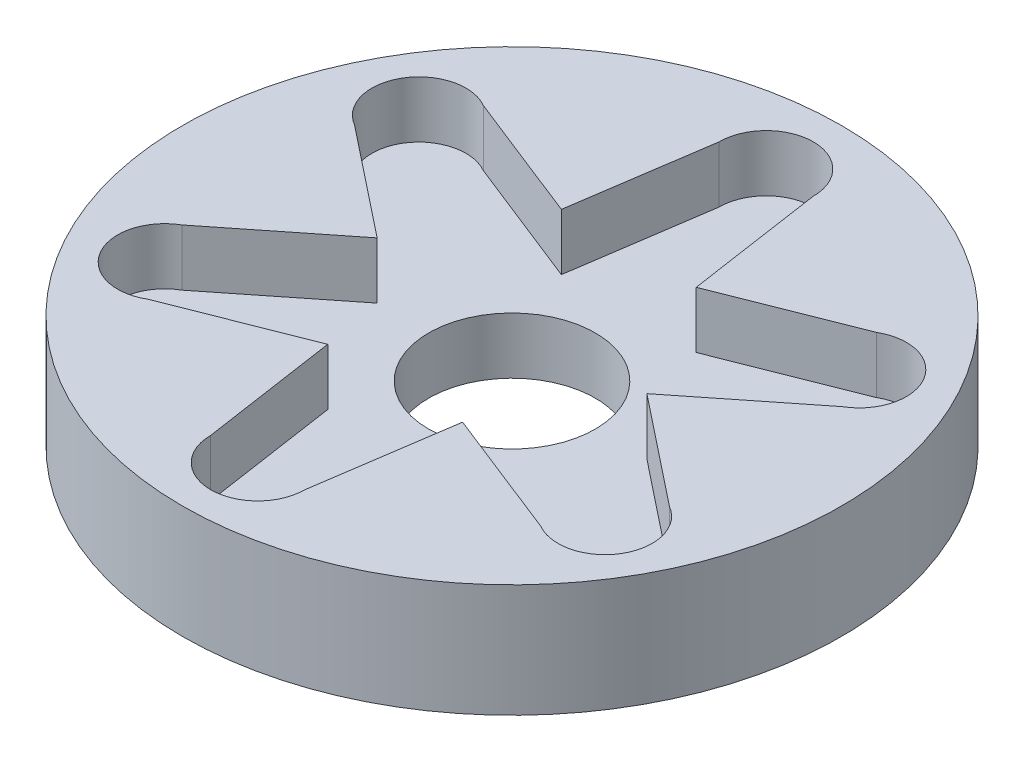
SolidWorks part; units mm, degrees
ref_plane "Front Plane" through (0, 0, 0) normal (0, 0, 1) x (1, 0, 0)
ref_plane "Top Plane" through (0, 0, 0) normal (0, 1, 0) x (1, 0, 0)
ref_plane "Right Plane" through (0, 0, 0) normal (1, 0, 0) x (0, 0, -1)
sketch "Sketch1" plane through (0, 0, 0) normal (0, 1, 0) x (1, 0, 0)
  line L0 (0, 0) -> (0, 16)
  line L2 (0, 13.5) -> (-2.5, 13.5)
  line L3 (0, 13.5) -> (2.5, 13.5)
  line L4 (-2.5, 13.5) -> (-4.5, 0)
  line L5 (2.5, 13.5) -> (4.5, 0)
  line L6 (0, 0) -> (13.8564, 8)
  line L8 (11.6913, 6.75) -> (10.4413, 8.9151)
  line L9 (11.6913, 6.75) -> (12.9413, 4.5849)
  line L10 (10.4413, 8.9151) -> (-2.25, 3.8971)
  line L11 (12.9413, 4.5849) -> (2.25, -3.8971)
  line L12 (0, 0) -> (13.8564, -8)
  line L14 (11.6913, -6.75) -> (12.9413, -4.5849)
  line L15 (11.6913, -6.75) -> (10.4413, -8.9151)
  line L16 (12.9413, -4.5849) -> (2.25, 3.8971)
  line L17 (10.4413, -8.9151) -> (-2.25, -3.8971)
  line L18 (0, 0) -> (0, -16)
  line L20 (0, -13.5) -> (2.5, -13.5)
  line L21 (0, -13.5) -> (-2.5, -13.5)
  line L22 (2.5, -13.5) -> (4.5, 0)
  line L23 (-2.5, -13.5) -> (-4.5, 0)
  line L24 (0, 0) -> (-13.8564, -8)
  line L26 (-11.6913, -6.75) -> (-10.4413, -8.9151)
  line L27 (-11.6913, -6.75) -> (-12.9413, -4.5849)
  line L28 (-10.4413, -8.9151) -> (2.25, -3.8971)
  line L29 (-12.9413, -4.5849) -> (-2.25, 3.8971)
  line L30 (0, 0) -> (-13.8564, 8)
  line L32 (-11.6913, 6.75) -> (-12.9413, 4.5849)
  line L33 (-11.6913, 6.75) -> (-10.4413, 8.9151)
  line L34 (-12.9413, 4.5849) -> (-2.25, -3.8971)
  line L35 (-10.4413, 8.9151) -> (2.25, 3.8971)
  circle A1 centre (0, 13.5) radius 2.5
  circle A3 centre (11.6913, 6.75) radius 2.5
  circle A5 centre (11.6913, -6.75) radius 2.5
  circle A7 centre (0, -13.5) radius 2.5
  circle A9 centre (-11.6913, -6.75) radius 2.5
  circle A10 centre (0, 0) radius 4.425
  circle A11 centre (-11.6913, 6.75) radius 2.5
  circle A12 centre (0, 0) radius 17.5
  point P53 (0, 0)
  dimension "D1" = 8.85
  dimension "D7" = 35
  dimension "D2" = 16
  dimension "D3" = 2.5
  dimension "D4" = 2.5
  dimension "D5" = 2.5
  dimension "D6" = 6
extrude "Boss-Extrude3" add sketch "Sketch1" along normal blind 6 contours A12 A11 L35 L4 A1 L5 L10 A3 L11 L16 A5 L17 L22 A7 L23 L28 A9 L29 L34 region at (-17.005, 0, 0)
extrude "Boss-Extrude5" add sketch "Sketch1<11>" along normal blind 3 contours L33 A11 L30 | L30 A11 L32 | L32 A11 L30 | L30 A11 L33 | A11 L30 L4 L35 | A11 L34 L29 L30 | L35 L4 L29 L10 | A10 L30 L4 L23 L24 | A10 L0 L10 L29 L30 | L29 L34 L23 L4 | A9 L24 L34 L29 | L24 A9 L27 | L27 A9 L24 | L24 A9 L26 | L26 A9 L24 | A9 L28 L23 L24 | A10 L24 L34 L17 L18 | L34 L23 L28 L17 | A7 L18 L28 L23 | A7 L22 L17 L18 | A10 L18 L28 L11 L12 | L28 L17 L22 L11 | L18 A7 L21 | L20 A7 L18 | L21 A7 L18 | L18 A7 L20 | A5 L12 L22 L17 | L15 A5 L12 | L14 A5 L12 | L12 A5 L15 | L12 A5 L14 | A5 L16 L11 L12 | A10 L12 L22 L5 L6 | L22 L11 L16 L5 | A3 L6 L16 L11 | A10 L6 L16 L35 L0 | L10 L35 L16 L5 | A3 L10 L5 L6 | L8 A3 L6 | L6 A3 L9 | L9 A3 L6 | L6 A3 L8 | A1 L0 L10 L5 | A1 L4 L35 L0 | L0 A1 L2 | L2 A1 L0 | L0 A1 L3 | L3 A1 L0 | A5 region at (-1.061, 0, -14.561) region at (1.061, 0, -12.439) region at (-1.061, 0, -12.439) region at (1.061, 0, -14.561) region at (1.6102, 0, -8.4409) region at (-1.6102, 0, -8.4409) region at (1.1071, 0, -4.2965) region at (-0.0488, 0, -4.6059) region at (-2.6346, 0, -4.5633) region at (2.6346, 0, -4.5633) region at (-6.5049, 0, -5.6149) region at (6.5049, 0, -5.6149) region at (-4.013, 0, -2.2611) region at (-5.2692, 0, 0) region at (-8.1151, 0, -2.826) region at (-10.2419, 0, -7.1384) region at (-12.0797, 0, -8.1994) region at (5.2692, 0, 0) region at (4.2749, 0, -1.1896) region at (8.1151, 0, -2.826) region at (12.0797, 0, -8.1994) region at (10.2419, 0, -7.1384) region at (-8.1151, 0, 2.826) region at (-11.303, 0, -5.3006) region at (-13.1407, 0, -6.3616) region at (11.303, 0, -5.3006) region at (8.1151, 0, 2.826) region at (13.1407, 0, -6.3616) region at (3.9644, 0, 2.3452) region at (-0.0488, 0, 4.6059) region at (-2.6346, 0, 4.5633) region at (-6.5049, 0, 5.6149) region at (-11.303, 0, 5.3006) region at (-13.1407, 0, 6.3616) region at (2.6346, 0, 4.5633) region at (6.5049, 0, 5.6149) region at (13.1407, 0, 6.3616) region at (11.303, 0, 5.3006) region at (1.6102, 0, 8.4409) region at (-1.6102, 0, 8.4409) region at (-10.2419, 0, 7.1384) region at (-12.0797, 0, 8.1994) region at (10.2419, 0, 7.1384) region at (12.0797, 0, 8.1994) region at (1.061, 0, 12.439) region at (-1.061, 0, 12.439) region at (-1.061, 0, 14.561) region at (1.061, 0, 14.561)
sketch "Sketch1<11>" plane through (0, 0, 0) normal (0, 1, 0) x (1, 0, 0) same geometry as "Sketch1"
